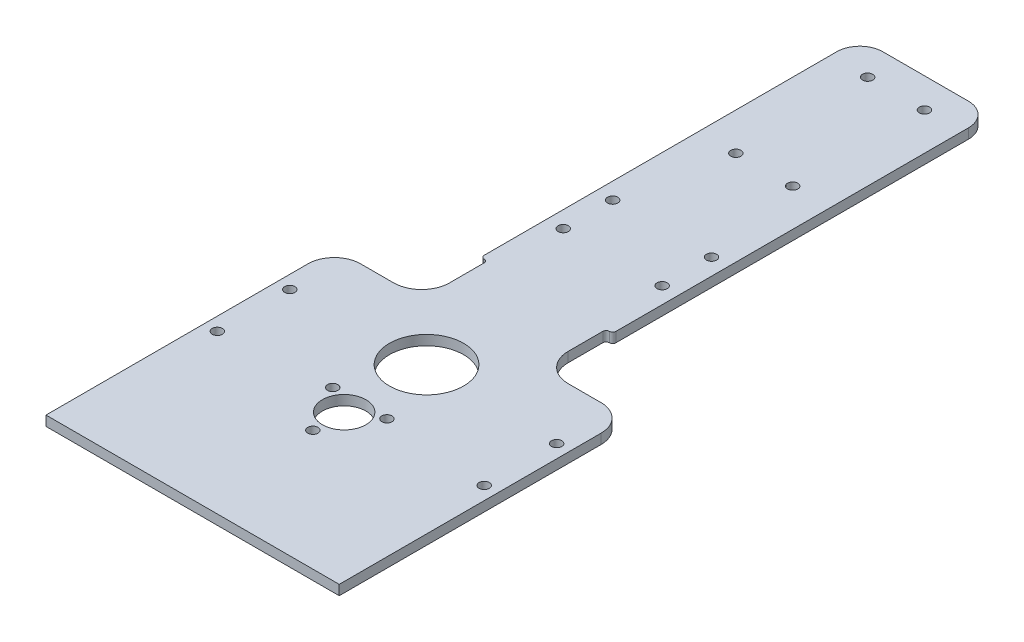
SolidWorks part; units mm, degrees
ref_plane "前视基准面" through (0, 0, 0) normal (0, 0, 1) x (1, 0, 0)
ref_plane "上视基准面" through (0, 0, 0) normal (0, 1, 0) x (1, 0, 0)
ref_plane "右视基准面" through (0, 0, 0) normal (1, 0, 0) x (0, 0, -1)
sketch "草图1" plane through (0, 0, 0) normal (0, 1, 0) x (1, 0, 0)
  line L1 (-100, 100) -> (100, 100)
  line L2 (-100, 100) -> (-100, -100)
  line L3 (-100, -100) -> (100, -100)
  line L4 (100, 100) -> (100, -100)
  line L5 (-100, 100) -> (100, -100) construction
  line L6 (-100, -100) -> (100, 100) construction
  point P0 (0, 0)
  dimension "D1" = 200
  dimension "D2" = 200
extrude "凸台-拉伸1" add sketch "草图1" along normal blind 3
sketch "草图2" plane through (0, 3, 0) normal (0, 1, 0) x (1, 0, 0)
  line L0 (0, 0) -> (0, 91) construction
  line L1 (-100, -100) -> (100, -100) construction
  line L2 (100, 100) -> (-100, 100) construction
  line L3 (-100, 0) -> (100, 0) construction
  line L5 (-100, 100) -> (-100, -100) construction
  line L6 (100, -100) -> (100, 100) construction
  line L7 (-29.5, 0) -> (29.5, 0) construction
  line L8 (-10, 100) -> (10, 100) construction
  line L9 (-10, 100) -> (-10, -100) construction
  line L10 (10, 100) -> (10, -100) construction
  line L11 (0, 0) -> (0, -29) construction
  line L13 (0, -29) -> (0, -32) construction
  circle A0 centre (-29.5, 0) radius 22.5 construction
  circle A1 centre (29.5, 0) radius 22.5 construction
  circle A2 centre (0, -29) radius 10.05 construction
  circle A3 centre (29.5, 0) radius 9.5 construction
  circle A4 centre (29.5, 0) radius 8 construction
  circle A5 centre (-29.5, 0) radius 8 construction
  circle A6 centre (-29.5, 0) radius 9.5 construction
  circle A7 centre (29.5, 9.5) radius 1.5
  circle A8 centre (21.5, 0) radius 1.5
  circle A9 centre (29.5, -9.5) radius 1.5
  circle A10 centre (37.5, 0) radius 1.5
  circle A11 centre (-29.5, -9.5) radius 1.5
  circle A12 centre (-37.5, 0) radius 1.5
  circle A13 centre (-21.5, 0) radius 1.5
  circle A14 centre (-29.5, 9.5) radius 1.5
  point P16 (0, 0)
  dimension "D1" = 45
  dimension "D3" = 20.1
  dimension "D4" = 19
  dimension "D5" = 16
  dimension "D6" = 3
  dimension "D7" = 3
  dimension "D2" = 20
  dimension "D9" = 3
  dimension "D10" = 29
extrude "切除-拉伸2" cut sketch "草图2" against normal blind 10
sketch "草图4" plane through (0, 3, 0) normal (0, 1, 0) x (1, 0, 0)
  line L0 (0, 0) -> (0, 91) construction
  line L1 (100, 100) -> (-100, 100) construction
  line L2 (-10, 100) -> (10, 100)
  line L3 (-10, 100) -> (-10, -100) construction
  line L4 (-100, -100) -> (100, -100) construction
  line L5 (10, 100) -> (10, -100) construction
  line L6 (21.5, 0) -> (37.5, 0)
  line L7 (-29.5, 0) -> (0, 0) construction
  line L8 (0, -29) -> (0, 0) construction
  circle A0 centre (0, -29) radius 11.25
  circle A1 centre (29.5, 0) radius 8 construction
  circle A2 centre (29.5, 0) radius 9.5 construction
  circle A3 centre (29.5, 0) radius 22.5 construction
  circle A4 centre (-29.5, 0) radius 9.5 construction
  circle A5 centre (-29.5, 0) radius 8 construction
  circle A6 centre (-29.5, 0) radius 22.5 construction
  dimension "D1" = 22.5
  dimension "D2" = 19
  dimension "D3" = 16
  dimension "D4" = 45
sketch "草图5" plane through (0, 3, 0) normal (0, 1, 0) x (1, 0, 0)
  line L0 (-44.5, -100) -> (-100, -100)
  line L2 (44.5, 0) -> (44.5, -100)
  line L4 (-20, 47.5) -> (-20, 24.995)
  line L6 (-44.5, 0) -> (-44.5, -100)
  line L7 (-100, -100) -> (100, -100) construction
  line L8 (20, 47.5) -> (20, 24.995)
  line L9 (-100, -100) -> (-100, 100)
  line L10 (0, 0) -> (0, 91) construction
  line L11 (0, 47.5) -> (-20, 47.5)
  line L12 (44.5, -100) -> (-44.5, -100)
  line L13 (0, 47.5) -> (20, 47.5)
  line L14 (-100, 100) -> (100, 100)
  line L15 (100, 100) -> (100, -100)
  line L16 (100, -100) -> (44.5, -100)
  arc A0 (29.8, 14.997) -> (44.5, 0) centre (29.5, 0) cw
  arc A1 (20, 24.995) -> (29.8, 14.997) centre (30, 24.995) ccw
  arc A2 (-29.8, 14.997) -> (-44.5, 0) centre (-29.5, 0) ccw
  arc A3 (-20, 24.995) -> (-29.8, 14.997) centre (-30, 24.995) cw
  line M11 (100, -100) -> (100, 100)
  line M12 (100, 100) -> (-100, 100)
  line M13 (-100, 100) -> (-100, -100)
  line M14 (-100, -100) -> (100, -100)
  dimension "D1" = 10
  dimension "D2" = 15
extrude "切除-拉伸3" cut sketch "草图5" against normal blind 10 contours A3 L4 L11 L13 L8 A1 A0 L2 L6 A2 M14 M11 M12 M13 region at (-72.25, 3, 97.1716)
sketch "草图6" plane through (0, 0, 0) normal (0, -1, 0) x (1, 0, 0)
  line L0 (20, -47.5) -> (-20, -47.5) construction
  line L7 (-20, -47.5) -> (-20, -24.995) construction
  circle A1 centre (-15, -42.5) radius 1.55
  circle A2 centre (-15, -27.5) radius 1.55
  circle A3 centre (15, -27.5) radius 1.55
  circle A4 centre (15, -42.5) radius 1.55
  dimension "D1" = 3.1
  dimension "D2" = 5
  dimension "D3" = 5
  dimension "D4" = 30
extrude "φ3.1通孔1" cut sketch "草图6" against normal blind 10
sketch "草图9" plane through (0, 3, 0) normal (0, 1, 0) x (1, 0, 0)
  line L0 (-20, 47.5) -> (-20, 26.3383)
  line L4 (-20, 47.5) -> (20, 47.5)
  line L5 (20, 47.5) -> (20, 26.3383)
  line L8 (12.2609, 20.995) -> (-12.2609, 20.995)
  arc A0 (-18.8003, 24.5054) -> (-13.4605, 21.3948) centre (-29.5, 0) cw
  arc A1 (18.8003, 24.5054) -> (13.4605, 21.3948) centre (29.5, 0) ccw
  arc A2 (18.8003, 24.5054) -> (20, 26.3383) centre (18, 26.3383) ccw
  arc A3 (13.4605, 21.3948) -> (12.2609, 20.995) centre (12.2609, 22.995) cw
  arc A4 (-12.2609, 20.995) -> (-13.4605, 21.3948) centre (-12.2609, 22.995) cw
  arc A5 (-18.8003, 24.5054) -> (-20, 26.3383) centre (-18, 26.3383) cw
  point P20 (-20, 24.995)
  dimension "D1" = 2
sketch "草图11" plane through (0, 3, 0) normal (0, 1, 0) x (1, 0, 0)
  line L0 (44.5, -17.5) -> (44.5, -100)
  line L1 (20, 47.5) -> (20, 7.5)
  line L2 (-44.5, 0) -> (-44.5, -100) construction
  line L3 (-44.5, -17.5) -> (-44.5, -100)
  line L4 (0, 47.5) -> (0, -100) construction
  line L5 (20, 47.5) -> (-20, 47.5) construction
  line L6 (-44.5, -100) -> (44.5, -100) construction
  line L7 (18, -4) -> (18, 6.5)
  line L8 (20, 7.5) -> (19, 7.5)
  line L9 (-39.5, -12.5) -> (-44.5, -12.5)
  line L10 (26.5, -12.5) -> (39.5, -12.5)
  line L11 (20, 47.5) -> (101.1331, 47.5)
  line L12 (101.1331, 47.5) -> (101.1331, -100)
  line L13 (101.1331, -100) -> (44.5, -100)
  line L14 (-20, 47.5) -> (-20, 7.5)
  line L15 (-20, 7.5) -> (-19, 7.5)
  line L16 (-18, -4) -> (-18, 6.5)
  line L17 (-26.5, -12.5) -> (-39.5, -12.5)
  line L18 (-44.5, -12.5) -> (-44.5, -17.5)
  line L19 (-101.1331, -100) -> (-44.5, -100)
  line L20 (-101.1331, 47.5) -> (-101.1331, -100)
  line L21 (-20, 47.5) -> (-101.1331, 47.5)
  line L22 (39.5, -12.5) -> (44.5, -12.5)
  line L23 (44.5, 0) -> (44.5, -100) construction
  line L24 (44.5, -12.5) -> (44.5, -17.5)
  arc A0 (26.5, -12.5) -> (18, -4) centre (26.5, -4) cw
  circle A2 centre (29.5, -9.5) radius 1.5
  circle A4 centre (21.5, 0) radius 1.5
  arc A5 (18, 6.5) -> (19, 7.5) centre (19, 6.5) cw
  arc A6 (-18, 6.5) -> (-19, 7.5) centre (-19, 6.5) ccw
  arc A7 (-26.5, -12.5) -> (-18, -4) centre (-26.5, -4) ccw
  point P21 (-44.5, -12.5)
  dimension "D1" = 8.5
  dimension "D2" = 1
extrude "切除-拉伸6" cut sketch "草图11" against normal up to next
extrude "φ20.5落弹孔" cut sketch "草图4" against normal up to next contours A0 region at (0, 3, 29)
fillet "圆角1" radius 1 2 edges at (-20, 1.5, -7.5) (20, 1.5, -7.5)
sketch "草图12" plane through (0, 0, -47.5) normal (0, 0, -1) x (-1, 0, 0)
  line L0 (-20, 3) -> (-20, 0)
  line L1 (-20, 0) -> (20, 0)
  line L2 (20, 0) -> (20, 3)
  line L3 (20, 3) -> (-20, 3)
extrude "凸台-拉伸2" add sketch "草图12" along normal blind 75
fillet "圆角2" radius 7 2 edges at (-20, 1.5, -122.5) (20, 1.5, -122.5)
sketch "草图13" plane through (0, 3, 0) normal (0, 1, 0) x (1, 0, 0)
  line L0 (-20, 115.5) -> (-20, 8.5) construction
  line L1 (0, 122.5) -> (0, 107.278)
  line L2 (-13, 122.5) -> (13, 122.5) construction
  circle A0 centre (-8.625, 73.5) radius 1.55
  circle A1 centre (-15, 42.5) radius 1.55
  circle A2 centre (-8.625, 113.5) radius 1.55
  circle A3 centre (8.625, 73.5) radius 1.55
  circle A4 centre (8.625, 113.5) radius 1.55
  dimension "D3" = 3.1
  dimension "D5" = 3.1
  dimension "D1" = 31
  dimension "D2" = 11.375
  dimension "D4" = 40
extrude "φ3.1通孔3" cut sketch "草图13" against normal blind 10 contours A2 | A4 | A3 | A0 region at (-8.625, 3, -73.5) region at (-8.625, 3, -113.5) region at (8.625, 3, -73.5) region at (8.625, 3, -113.5)
sketch "草图14" plane through (0, 3, 0) normal (0, 1, 0) x (1, 0, 0)
  line L1 (0, -43) -> (32.1524, -43) construction
  circle A0 centre (0, -29) radius 11 construction
  circle A1 centre (0, -54) radius 9.5 construction
  circle A2 centre (0, -63.5) radius 1.55
  circle A3 centre (-8.2272, -49.25) radius 1.55
  circle A5 centre (8.2272, -49.25) radius 1.55
  circle A6 centre (0, -54) radius 6.6
  point P19 (0, -54)
  dimension "D1" = 22
  dimension "D2" = 25
  dimension "D3" = 19
  dimension "D4" = 3.1
  dimension "D5" = 3
  dimension "D6" = 13.2
extrude "2006电机固定" cut sketch "草图14" against normal up to next
sketch "草图15" plane through (0, 3, 0) normal (0, 1, 0) x (1, 0, 0)
  circle A0 centre (0, -54) radius 32.5 construction
  circle A1 centre (0, -29) radius 11
  circle A2 centre (0, -29) radius 10
  circle A3 centre (0, -49) radius 37
  circle A4 centre (0, -54) radius 35
  circle A5 centre (0, -49) radius 33.5
  circle A6 centre (15, -19.0459) radius 1.5
  circle A7 centre (-15, -19.0459) radius 1.5
  point P12 (0, -15.5)
  dimension "D1" = 65
  dimension "D2" = 22
  dimension "D3" = 20
  dimension "D4" = 74
  dimension "D5" = 70
  dimension "D6" = 67
  dimension "D7" = 3
  dimension "D9" = 15
sketch "草图16" plane through (0, 3, 0) normal (0, 1, 0) x (1, 0, 0)
  circle A0 centre (0, -54) radius 35
  circle A1 centre (0, -54) radius 38
  dimension "D1" = 70
  dimension "D2" = 76
fillet "圆角3" radius 8 2 edges at (44.5, 1.5, 12.5) (-44.5, 1.5, 12.5)
sketch "草图17" plane through (0, 3, 0) normal (0, 1, 0) x (1, 0, 0)
  line L0 (-44.5, -20.5) -> (-44.5, -100) construction
  circle A0 centre (-40.5, -30) radius 1.55
  circle A1 centre (-40.5, -52) radius 1.55
  dimension "D2" = 3.1
  dimension "D4" = 3.1
  dimension "D1" = 30
  dimension "D3" = 4
  dimension "D5" = 22
extrude "切除-拉伸7" cut sketch "草图17" against normal through all
mirror "镜向1" about plane through (0, 0, 0) normal (1, 0, 0) of "切除-拉伸7"
